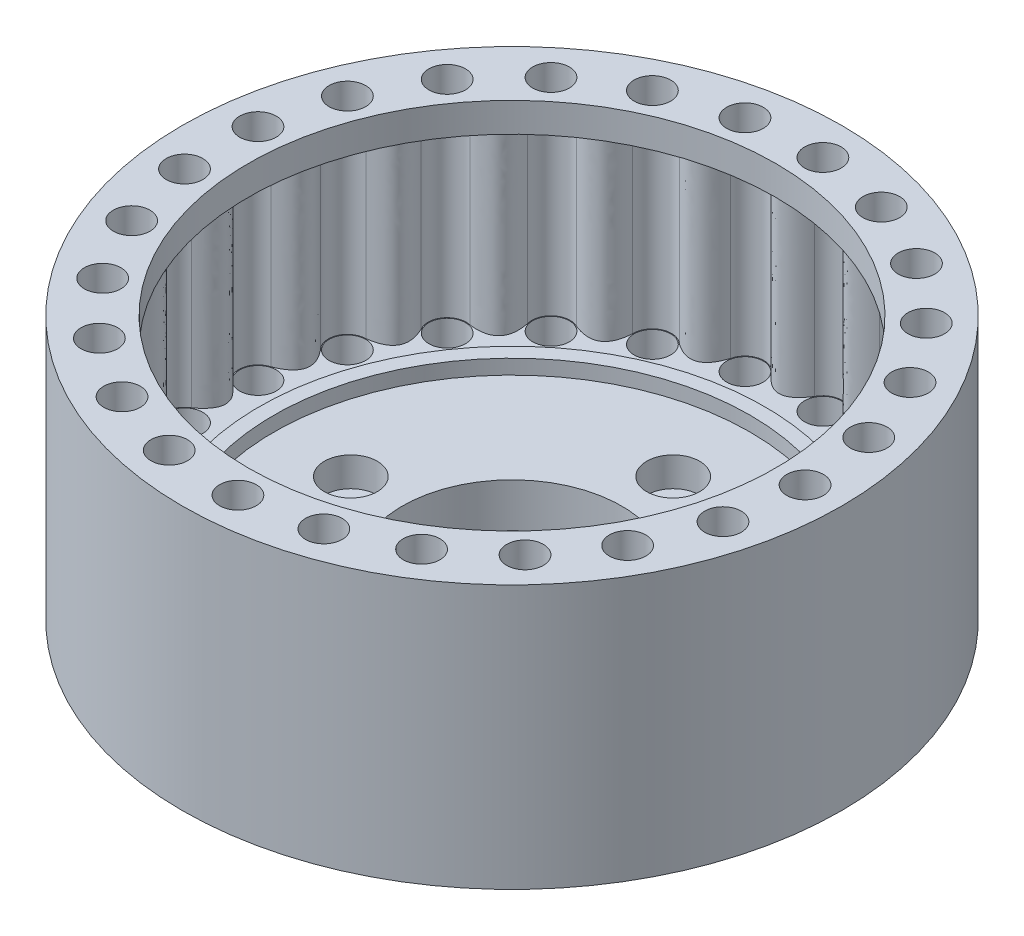
SolidWorks part; units mm, degrees
ref_plane "Front Plane" through (0, 0, 0) normal (0, 0, 1) x (1, 0, 0)
ref_plane "Top Plane" through (0, 0, 0) normal (0, 1, 0) x (1, 0, 0)
ref_plane "Right Plane" through (0, 0, 0) normal (1, 0, 0) x (0, 0, -1)
sketch "Sketch1" plane through (0, 0, 0) normal (0, 1, 0) x (1, 0, 0)
  circle A1 centre (0, 0) radius 45
  circle A2 centre (0, 0) radius 22 construction
  circle A3 centre (0, -22) radius 2
  circle A5 centre (-22, 0) radius 2
  circle A6 centre (0, 22) radius 2
  circle A7 centre (22, 0) radius 2
  point P15 (0, 0)
  dimension "D1" = 90
  dimension "D2" = 44
  dimension "D3" = 4
  dimension "D4" = 4
  dimension "D5" = 90
  dimension "D6" = 22
extrude "Boss-Extrude1" add sketch "Sketch1" along normal blind 6
sketch "Sketch2" plane through (0, 6, 0) normal (0, 1, 0) x (1, 0, 0)
  circle A0 centre (0, 0) radius 22 construction
  circle A1 centre (0, 22) radius 3.61
  circle A2 centre (22, 0) radius 3.61
  circle A3 centre (0, -22) radius 3.61
  circle A4 centre (-22, 0) radius 3.61
  point P14 (0, 0)
  dimension "D1" = 44
  dimension "D2" = 7.22
  dimension "D4" = 22
  dimension "D5" = 90
  dimension "D3" = 4
extrude "Cut-Extrude1" cut sketch "Sketch2" against normal blind 4
sketch "Sketch4" plane through (0, 6, 0) normal (0, 1, 0) x (1, 0, 0)
  circle A0 centre (0, 0) radius 15
  dimension "D1" = 30
extrude "Cut-Extrude2" cut sketch "Sketch4" against normal through all
sketch "Sketch5" plane through (0, 6, 0) normal (0, 1, 0) x (1, 0, 0)
  circle A0 centre (40, 0) radius 2.5
  circle A1 centre (38.7433, -9.9476) radius 2.5
  circle A2 centre (35.0523, -19.2701) radius 2.5
  circle A3 centre (29.1587, -27.3819) radius 2.5
  circle A4 centre (21.4331, -33.7731) radius 2.5
  circle A5 centre (12.3607, -38.0423) radius 2.5
  circle A6 centre (2.5116, -39.9211) radius 2.5
  circle A7 centre (-7.4953, -39.2915) radius 2.5
  circle A8 centre (-17.0312, -36.1931) radius 2.5
  circle A9 centre (-25.497, -30.8205) radius 2.5
  circle A10 centre (-32.3607, -23.5114) radius 2.5
  circle A11 centre (-37.1911, -14.725) radius 2.5
  circle A12 centre (-39.6846, -5.0133) radius 2.5
  circle A13 centre (-39.6846, 5.0133) radius 2.5
  circle A14 centre (-37.1911, 14.725) radius 2.5
  circle A15 centre (-32.3607, 23.5114) radius 2.5
  circle A16 centre (-25.497, 30.8205) radius 2.5
  circle A17 centre (-17.0312, 36.1931) radius 2.5
  circle A18 centre (-7.4953, 39.2915) radius 2.5
  circle A19 centre (2.5116, 39.9211) radius 2.5
  circle A20 centre (12.3607, 38.0423) radius 2.5
  circle A21 centre (21.4331, 33.7731) radius 2.5
  circle A22 centre (29.1587, 27.3819) radius 2.5
  circle A23 centre (35.0523, 19.2701) radius 2.5
  circle A24 centre (38.7433, 9.9476) radius 2.5
  point P53 (0, 0)
  dimension "D2" = 5
  dimension "D1" = 40
  dimension "D3" = 25
extrude "Cut-Extrude3" cut sketch "Sketch5" against normal blind 4
sketch "Sketch6" plane through (0, 6, 0) normal (0, 1, 0) x (1, 0, 0)
  circle A0 centre (0, 0) radius 32.5
  circle A1 centre (0, 0) radius 34.5
  dimension "D1" = 65
  dimension "D2" = 69
extrude "Boss-Extrude2" add sketch "Sketch6" along normal blind 2
sketch "Sketch7" plane through (0, 6, 0) normal (0, 1, 0) x (1, 0, 0)
  line L0 (0, 0) -> (35.0523, -19.2701) construction
  line L1 (0, 0) -> (27.3363, -25.6705) construction
  line L2 (35.0523, -19.2701) -> (34.7909, -21.7565) construction
  line L3 (29.1587, -27.3819) -> (31.4426, -26.365) construction
  line L4 (0, 0) -> (31.5517, -22.9236) construction
  circle A0 centre (35.0523, -19.2701) radius 2.5 construction
  circle A1 centre (38.7433, -9.9476) radius 2.5 construction
  circle A2 centre (40, 0) radius 2.5 construction
  circle A3 centre (38.7433, 9.9476) radius 2.5 construction
  circle A4 centre (35.0523, 19.2701) radius 2.5 construction
  circle A5 centre (29.1587, 27.3819) radius 2.5 construction
  circle A6 centre (21.4331, 33.7731) radius 2.5 construction
  circle A7 centre (12.3607, 38.0423) radius 2.5 construction
  circle A8 centre (2.5116, 39.9211) radius 2.5 construction
  circle A9 centre (-7.4953, 39.2915) radius 2.5 construction
  circle A10 centre (-17.0312, 36.1931) radius 2.5 construction
  circle A11 centre (-25.497, 30.8205) radius 2.5 construction
  circle A12 centre (-32.3607, 23.5114) radius 2.5 construction
  circle A13 centre (-37.1911, 14.725) radius 2.5 construction
  circle A14 centre (-39.6846, 5.0133) radius 2.5 construction
  circle A15 centre (-39.6846, -5.0133) radius 2.5 construction
  circle A16 centre (-37.1911, -14.725) radius 2.5 construction
  circle A17 centre (-32.3607, -23.5114) radius 2.5 construction
  circle A18 centre (-25.497, -30.8205) radius 2.5 construction
  circle A19 centre (-17.0312, -36.1931) radius 2.5 construction
  circle A20 centre (-7.4953, -39.2915) radius 2.5 construction
  circle A21 centre (2.5116, -39.9211) radius 2.5 construction
  circle A22 centre (12.3607, -38.0423) radius 2.5 construction
  circle A23 centre (21.4331, -33.7731) radius 2.5 construction
  circle A24 centre (29.1587, -27.3819) radius 2.5 construction
  arc A25 (34.7909, -21.7565) -> (37.0115, -17.7173) centre (35.0523, -19.2701) ccw construction
  arc A26 (39.1085, -12.4208) -> (40.2548, -7.9563) centre (38.7433, -9.9476) ccw construction
  arc A27 (40.9688, -2.3047) -> (40.9688, 2.3047) centre (40, 0) ccw construction
  arc A28 (40.2548, 7.9563) -> (39.1085, 12.4208) centre (38.7433, 9.9476) ccw construction
  arc A29 (37.0115, 17.7173) -> (34.7909, 21.7565) centre (35.0523, 19.2701) ccw construction
  arc A30 (31.4426, 26.365) -> (28.2873, 29.7251) centre (29.1587, 27.3819) ccw construction
  arc A31 (23.8981, 33.3562) -> (20.0063, 35.826) centre (21.4331, 33.7731) ccw construction
  arc A32 (14.8519, 38.2515) -> (10.4682, 39.6758) centre (12.3607, 38.0423) ccw construction
  arc A33 (4.8726, 40.7432) -> (0.2723, 41.0327) centre (2.5116, 39.9211) ccw construction
  arc A34 (-5.4129, 40.675) -> (-9.9406, 39.8113) centre (-7.4953, 39.2915) ccw construction
  arc A35 (-15.3583, 38.0509) -> (-19.529, 36.0884) centre (-17.0312, 36.1931) ccw construction
  arc A36 (-24.3387, 33.036) -> (-27.8903, 30.098) centre (-25.497, 30.8205) ccw construction
  arc A37 (-31.7898, 25.9454) -> (-34.4991, 22.2163) centre (-32.3607, 23.5114) ccw construction
  arc A38 (-37.2434, 17.2244) -> (-38.9402, 12.9388) centre (-37.1911, 14.725) ccw construction
  arc A39 (-40.3569, 7.4212) -> (-40.9346, 2.8483) centre (-39.6846, 5.0133) ccw construction
  arc A40 (-40.9346, -2.8483) -> (-40.3569, -7.4212) centre (-39.6846, -5.0133) ccw construction
  arc A41 (-38.9402, -12.9388) -> (-37.2434, -17.2244) centre (-37.1911, -14.725) ccw construction
  arc A42 (-34.4991, -22.2163) -> (-31.7898, -25.9454) centre (-32.3607, -23.5114) ccw construction
  arc A43 (-27.8903, -30.098) -> (-24.3387, -33.036) centre (-25.497, -30.8205) ccw construction
  arc A44 (-19.529, -36.0884) -> (-15.3583, -38.0509) centre (-17.0312, -36.1931) ccw construction
  arc A45 (-9.9406, -39.8113) -> (-5.4129, -40.675) centre (-7.4953, -39.2915) ccw construction
  arc A46 (0.2723, -41.0327) -> (4.8726, -40.7432) centre (2.5116, -39.9211) ccw construction
  arc A47 (10.4682, -39.6758) -> (14.8519, -38.2515) centre (12.3607, -38.0423) ccw construction
  arc A48 (20.0063, -35.826) -> (23.8981, -33.3562) centre (21.4331, -33.7731) ccw construction
  arc A49 (28.2873, -29.7251) -> (31.4426, -26.365) centre (29.1587, -27.3819) ccw construction
  arc A51 (33.4936, -21.8672) -> (35.0523, -19.2701) centre (0, 0) ccw construction
  arc A53 (23.9272, -32.0545) -> (27.0032, -29.5098) centre (0, 0) ccw construction
  arc A54 (15.2038, -36.9979) -> (18.8161, -35.2981) centre (0, 0) ccw construction
  arc A55 (9.9601, -38.7401) -> (14.713, -37.1958) centre (0, 0) ccw construction
  arc A56 (5.5252, -39.6166) -> (9.4467, -38.8685) centre (0, 0) ccw construction
  arc A57 (-5.0261, -39.683) -> (5.0006, -39.6862) centre (0, 0) ccw construction
  arc A58 (-14.7369, -37.1863) -> (-10.4469, -38.6117) centre (0, 0) ccw construction
  arc A59 (-23.0917, -32.6615) -> (-22.9047, -32.7929) centre (0, 0) ccw construction
  arc A60 (-30.4888, -25.8927) -> (-27.756, -28.8029) centre (0, 0) ccw construction
  arc A61 (-35.9702, -17.4969) -> (-34.047, -20.9953) centre (0, 0) ccw construction
  arc A62 (-39.1915, -8.0018) -> (-38.1986, -11.8686) centre (0, 0) ccw construction
  arc A63 (-39.9502, 1.9961) -> (-39.9502, -1.9961) centre (0, 0) ccw construction
  arc A64 (-38.1986, 11.8686) -> (-39.1915, 8.0018) centre (0, 0) ccw construction
  arc A65 (-36.1986, 17.0195) -> (-38.0383, 12.3729) centre (0, 0) ccw construction
  arc A66 (-34.047, 20.9953) -> (-35.9702, 17.4969) centre (0, 0) ccw construction
  arc A67 (-27.756, 28.8029) -> (-30.4888, 25.8927) centre (0, 0) ccw construction
  arc A68 (-19.2589, 35.0585) -> (-23.0917, 32.6615) centre (0, 0) ccw construction
  arc A69 (-9.9351, 38.7465) -> (-14.7369, 37.1863) centre (0, 0) ccw construction
  arc A70 (-0.5163, 39.9967) -> (-5.0261, 39.683) centre (0, 0) ccw construction
  arc A71 (9.4467, 38.8685) -> (0.0129, 40) centre (0, 0) ccw construction
  arc A72 (18.8161, 35.2981) -> (15.2038, 36.9979) centre (0, 0) ccw construction
  arc A73 (27.0032, 29.5098) -> (23.9272, 32.0545) centre (0, 0) ccw construction
  arc A74 (33.4936, 21.8672) -> (30.8123, 25.5069) centre (0, 0) ccw construction
  arc A75 (37.8795, 12.8507) -> (36.4099, 16.5626) centre (0, 0) ccw construction
  arc A76 (39.8853, 3.0267) -> (39.2891, 7.5079) centre (0, 0) ccw construction
  arc A77 (39.385, -6.9875) -> (39.9219, -2.4988) centre (0, 0) ccw construction
  arc A78 (36.1876, -17.0428) -> (37.8795, -12.8507) centre (0, 0) ccw construction
  circle A79 centre (0, 0) radius 45
  arc A80 (34.7861, -21.8565) -> (37.0934, -17.6596) centre (35.0523, -19.2701) ccw
  arc A81 (39.1287, -12.5189) -> (40.3198, -7.88) centre (38.7433, -9.9476) ccw
  arc A82 (41.0127, -2.3947) -> (41.0127, 2.3947) centre (40, 0) ccw
  arc A83 (40.3198, 7.88) -> (39.1287, 12.5189) centre (38.7433, 9.9476) ccw
  arc A84 (37.0934, 17.6596) -> (34.7861, 21.8565) centre (35.0523, 19.2701) ccw
  arc A85 (31.5362, 26.3295) -> (28.2577, 29.8208) centre (29.1587, 27.3819) ccw
  arc A86 (23.9976, 33.3451) -> (19.9538, 35.9113) centre (21.4331, 33.7731) ccw
  arc A87 (14.9511, 38.2654) -> (10.3962, 39.7454) centre (12.3607, 38.0423) ccw
  arc A88 (4.9651, 40.7814) -> (0.1853, 41.0822) centre (2.5116, 39.9211) ccw
  arc A89 (-5.3328, 40.735) -> (-10.0373, 39.8376) centre (-7.4953, 39.2915) ccw
  arc A90 (-15.2956, 38.129) -> (-19.6291, 36.0898) centre (-17.0312, 36.1931) ccw
  arc A91 (-24.2974, 33.1273) -> (-27.9876, 30.0744) centre (-25.497, 30.8205) ccw
  arc A92 (-31.7724, 26.044) -> (-34.5875, 22.1694) centre (-32.3607, 23.5114) ccw
  arc A93 (-37.2511, 17.3243) -> (-39.0142, 12.8713) centre (-37.1911, 14.725) ccw
  arc A94 (-40.3892, 7.516) -> (-40.9895, 2.7645) centre (-39.6846, 5.0133) ccw
  arc A95 (-40.9895, -2.7645) -> (-40.3892, -7.516) centre (-39.6846, -5.0133) ccw
  arc A96 (-39.0142, -12.8713) -> (-37.2511, -17.3243) centre (-37.1911, -14.725) ccw
  arc A97 (-34.5875, -22.1694) -> (-31.7724, -26.044) centre (-32.3607, -23.5114) ccw
  arc A98 (-27.9876, -30.0744) -> (-24.2974, -33.1273) centre (-25.497, -30.8205) ccw
  arc A99 (-19.6291, -36.0898) -> (-15.2956, -38.129) centre (-17.0312, -36.1931) ccw
  arc A100 (-10.0373, -39.8376) -> (-5.3328, -40.735) centre (-7.4953, -39.2915) ccw
  arc A101 (0.1853, -41.0822) -> (4.9651, -40.7814) centre (2.5116, -39.9211) ccw
  arc A102 (10.3962, -39.7454) -> (14.9511, -38.2654) centre (12.3607, -38.0423) ccw
  arc A103 (19.9538, -35.9113) -> (23.9976, -33.3451) centre (21.4331, -33.7731) ccw
  arc A104 (28.2577, -29.8208) -> (31.5362, -26.3295) centre (29.1587, -27.3819) ccw
  spline S0 degree 2 poles (34.7909, -21.7565) (29.9865, -21.7865) (31.4426, -26.365) knots 0 0 0 1 1 1 construction
  spline S1 degree 2 poles (28.2873, -29.7251) (23.6264, -28.5594) (23.8981, -33.3562) knots 0 0 0 1 1 1 construction
  spline S2 degree 2 poles (20.0063, -35.826) (15.7817, -33.5378) (14.8519, -38.2515) knots 0 0 0 1 1 1 construction
  spline S3 degree 2 poles (10.4682, -39.6758) (6.9454, -36.4089) (4.8726, -40.7432) knots 0 0 0 1 1 1 construction
  spline S4 degree 2 poles (0.2723, -41.0327) (-2.3274, -36.9923) (-5.4129, -40.675) knots 0 0 0 1 1 1 construction
  spline S5 degree 2 poles (-9.9406, -39.8113) (-11.4538, -35.2513) (-15.3583, -38.0509) knots 0 0 0 1 1 1 construction
  spline S6 degree 2 poles (-19.529, -36.0884) (-19.8606, -31.2954) (-24.3387, -33.036) knots 0 0 0 1 1 1 construction
  spline S7 degree 2 poles (-27.8903, -30.098) (-27.0195, -25.373) (-31.7898, -25.9454) knots 0 0 0 1 1 1 construction
  spline S8 degree 2 poles (-34.4991, -22.2163) (-32.4807, -17.8564) (-37.2434, -17.2244) knots 0 0 0 1 1 1 construction
  spline S9 degree 2 poles (-38.9402, -12.9388) (-35.9009, -9.2178) (-40.3569, -7.4212) knots 0 0 0 1 1 1 construction
  spline S10 degree 2 poles (-40.9346, -2.8483) (-37.0654, 0) (-40.9346, 2.8483) knots 0 0 0 1 1 1 construction
  spline S11 degree 2 poles (-40.3569, 7.4212) (-35.9009, 9.2178) (-38.9402, 12.9388) knots 0 0 0 1 1 1 construction
  spline S12 degree 2 poles (-37.2434, 17.2244) (-32.4807, 17.8564) (-34.4991, 22.2163) knots 0 0 0 1 1 1 construction
  spline S13 degree 2 poles (-31.7898, 25.9454) (-27.0195, 25.373) (-27.8903, 30.098) knots 0 0 0 1 1 1 construction
  spline S14 degree 2 poles (-24.3387, 33.036) (-19.8606, 31.2954) (-19.529, 36.0884) knots 0 0 0 1 1 1 construction
  spline S15 degree 2 poles (-15.3583, 38.0509) (-11.4538, 35.2513) (-9.9406, 39.8113) knots 0 0 0 1 1 1 construction
  spline S16 degree 2 poles (-5.4129, 40.675) (-2.3274, 36.9923) (0.2723, 41.0327) knots 0 0 0 1 1 1 construction
  spline S17 degree 2 poles (4.8726, 40.7432) (6.9454, 36.4089) (10.4682, 39.6758) knots 0 0 0 1 1 1 construction
  spline S18 degree 2 poles (14.8519, 38.2515) (15.7817, 33.5378) (20.0063, 35.826) knots 0 0 0 1 1 1 construction
  spline S19 degree 2 poles (23.8981, 33.3562) (23.6264, 28.5594) (28.2873, 29.7251) knots 0 0 0 1 1 1 construction
  spline S20 degree 2 poles (31.4426, 26.365) (29.9865, 21.7865) (34.7909, 21.7565) knots 0 0 0 1 1 1 construction
  spline S21 degree 2 poles (37.0115, 17.7173) (34.4625, 13.6447) (39.1085, 12.4208) knots 0 0 0 1 1 1 construction
  spline S22 degree 2 poles (40.2548, 7.9563) (36.7731, 4.6455) (40.9688, 2.3047) knots 0 0 0 1 1 1 construction
  spline S23 degree 2 poles (40.9688, -2.3047) (36.7731, -4.6455) (40.2548, -7.9563) knots 0 0 0 1 1 1 construction
  spline S24 degree 2 poles (39.1085, -12.4208) (34.4625, -13.6447) (37.0115, -17.7173) knots 0 0 0 1 1 1 construction
  spline S25 degree 1 poles (39.1287, -12.5189) (37.0934, -17.6596) knots 0 0 1 1 construction
  spline S26 degree 1 poles (41.0127, -2.3947) (40.3198, -7.88) knots 0 0 1 1 construction
  spline S27 degree 1 poles (40.3198, 7.88) (41.0127, 2.3947) knots 0 0 1 1 construction
  spline S28 degree 1 poles (37.0934, 17.6596) (39.1287, 12.5189) knots 0 0 1 1 construction
  spline S29 degree 1 poles (31.5362, 26.3295) (34.7861, 21.8565) knots 0 0 1 1 construction
  spline S30 degree 1 poles (23.9976, 33.3451) (28.2577, 29.8208) knots 0 0 1 1 construction
  spline S31 degree 1 poles (14.9511, 38.2654) (19.9538, 35.9113) knots 0 0 1 1 construction
  spline S32 degree 1 poles (4.9651, 40.7814) (10.3962, 39.7454) knots 0 0 1 1 construction
  spline S33 degree 1 poles (-5.3328, 40.735) (0.1853, 41.0822) knots 0 0 1 1 construction
  spline S34 degree 1 poles (-15.2956, 38.129) (-10.0373, 39.8376) knots 0 0 1 1 construction
  spline S35 degree 1 poles (-24.2974, 33.1273) (-19.6291, 36.0898) knots 0 0 1 1 construction
  spline S36 degree 1 poles (-31.7724, 26.044) (-27.9876, 30.0744) knots 0 0 1 1 construction
  spline S37 degree 1 poles (-37.2511, 17.3243) (-34.5875, 22.1694) knots 0 0 1 1 construction
  spline S38 degree 1 poles (-40.3892, 7.516) (-39.0142, 12.8713) knots 0 0 1 1 construction
  spline S39 degree 1 poles (-40.9895, -2.7645) (-40.9895, 2.7645) knots 0 0 1 1 construction
  spline S40 degree 1 poles (-39.0142, -12.8713) (-40.3892, -7.516) knots 0 0 1 1 construction
  spline S41 degree 1 poles (-34.5875, -22.1694) (-37.2511, -17.3243) knots 0 0 1 1 construction
  spline S42 degree 1 poles (-27.9876, -30.0744) (-31.7724, -26.044) knots 0 0 1 1 construction
  spline S43 degree 1 poles (-19.6291, -36.0898) (-24.2974, -33.1273) knots 0 0 1 1 construction
  spline S44 degree 1 poles (-10.0373, -39.8376) (-15.2956, -38.129) knots 0 0 1 1 construction
  spline S45 degree 1 poles (0.1853, -41.0822) (-5.3328, -40.735) knots 0 0 1 1 construction
  spline S46 degree 1 poles (10.3962, -39.7454) (4.9651, -40.7814) knots 0 0 1 1 construction
  spline S47 degree 1 poles (19.9538, -35.9113) (14.9511, -38.2654) knots 0 0 1 1 construction
  spline S48 degree 1 poles (28.2577, -29.8208) (23.9976, -33.3451) knots 0 0 1 1 construction
  spline S49 degree 1 poles (34.7861, -21.8565) (31.5362, -26.3295) knots 0 0 1 1 construction
  spline S50 degree 3 poles (37.0934, -17.6596) (36.9928, -17.4988) (36.7956, -17.161) (36.4917, -16.5417) (36.2467, -15.8185) (36.1759, -15.0518) (36.3187, -14.3796) (36.6748, -13.7918) (37.2512, -13.2814) (37.9249, -12.9219) (38.5703, -12.6785) (38.9453, -12.5673) (39.1287, -12.5189) knots 0.000577 0.000577 0.000577 0.000577 0.063005 0.125433 0.250288 0.375144 0.5 0.624856 0.749712 0.874567 0.936995 0.999423 0.999423 0.999423 0.999423
  spline S51 degree 3 poles (40.3198, -7.88) (40.1824, -7.7493) (39.9074, -7.4711) (39.459, -6.9469) (39.0418, -6.3073) (38.7826, -5.5824) (38.7538, -4.8957) (38.9524, -4.2379) (39.3838, -3.6001) (39.947, -3.0844) (40.5116, -2.6882) (40.8472, -2.4872) (41.0127, -2.3947) knots 0.000577 0.000577 0.000577 0.000577 0.063005 0.125433 0.250288 0.375144 0.5 0.624856 0.749712 0.874567 0.936995 0.999423 0.999423 0.999423 0.999423
  spline S52 degree 3 poles (41.0127, 2.3947) (40.8472, 2.4872) (40.5116, 2.6882) (39.947, 3.0844) (39.3838, 3.6001) (38.9524, 4.2379) (38.7538, 4.8957) (38.7826, 5.5824) (39.0418, 6.3073) (39.459, 6.9469) (39.9074, 7.4711) (40.1824, 7.7493) (40.3198, 7.88) knots 0.000577 0.000577 0.000577 0.000577 0.063005 0.125433 0.250288 0.375144 0.5 0.624856 0.749712 0.874567 0.936995 0.999423 0.999423 0.999423 0.999423
  spline S53 degree 3 poles (39.1287, 12.5189) (38.9453, 12.5673) (38.5703, 12.6785) (37.9249, 12.9219) (37.2512, 13.2814) (36.6748, 13.7918) (36.3187, 14.3796) (36.1759, 15.0518) (36.2467, 15.8185) (36.4917, 16.5417) (36.7956, 17.161) (36.9928, 17.4988) (37.0934, 17.6596) knots 0.000577 0.000577 0.000577 0.000577 0.063005 0.125433 0.250288 0.375144 0.5 0.624856 0.749712 0.874567 0.936995 0.999423 0.999423 0.999423 0.999423
  spline S54 degree 3 poles (34.7861, 21.8565) (34.5964, 21.8578) (34.2055, 21.8722) (33.5199, 21.9475) (32.7779, 22.1281) (32.0927, 22.4791) (31.6016, 22.9599) (31.2961, 23.5755) (31.174, 24.3357) (31.2315, 25.0971) (31.3718, 25.7725) (31.4789, 26.1488) (31.5362, 26.3295) knots 0.000577 0.000577 0.000577 0.000577 0.063005 0.125433 0.250288 0.375144 0.5 0.624856 0.749712 0.874567 0.936995 0.999423 0.999423 0.999423 0.999423
  spline S55 degree 3 poles (28.2577, 29.8208) (28.0737, 29.7749) (27.6915, 29.6917) (27.0087, 29.594) (26.2451, 29.5845) (25.4941, 29.754) (24.8989, 30.0976) (24.4499, 30.6179) (24.1426, 31.3238) (24.0089, 32.0756) (23.9769, 32.7647) (23.987, 33.1557) (23.9976, 33.3451) knots 0.000577 0.000577 0.000577 0.000577 0.063005 0.125433 0.250288 0.375144 0.5 0.624856 0.749712 0.874567 0.936995 0.999423 0.999423 0.999423 0.999423
  spline S56 degree 3 poles (19.9538, 35.9113) (19.787, 35.8211) (19.4375, 35.6454) (18.8004, 35.3811) (18.0632, 35.1819) (17.2936, 35.1594) (16.6317, 35.3442) (16.0674, 35.7364) (15.5942, 36.3437) (15.2777, 37.0387) (15.0754, 37.6981) (14.9879, 38.0794) (14.9511, 38.2654) knots 0.000577 0.000577 0.000577 0.000577 0.063005 0.125433 0.250288 0.375144 0.5 0.624856 0.749712 0.874567 0.936995 0.999423 0.999423 0.999423 0.999423
  spline S57 degree 3 poles (10.3962, 39.7454) (10.257, 39.6165) (9.9622, 39.3595) (9.4108, 38.945) (8.7463, 38.5687) (8.0065, 38.3555) (7.3194, 38.3699) (6.6753, 38.6095) (6.0659, 39.08) (5.5866, 39.6745) (5.2266, 40.2629) (5.0471, 40.6104) (4.9651, 40.7814) knots 0.000577 0.000577 0.000577 0.000577 0.063005 0.125433 0.250288 0.375144 0.5 0.624856 0.749712 0.874567 0.936995 0.999423 0.999423 0.999423 0.999423
  spline S58 degree 3 poles (0.1853, 41.0822) (0.0826, 40.9227) (-0.1391, 40.6004) (-0.57, 40.0618) (-1.1201, 39.5321) (-1.7837, 39.1417) (-2.4527, 38.9847) (-3.1362, 39.0566) (-3.8434, 39.3608) (-4.4555, 39.8174) (-4.9506, 40.2977) (-5.2109, 40.5897) (-5.3328, 40.735) knots 0.000577 0.000577 0.000577 0.000577 0.063005 0.125433 0.250288 0.375144 0.5 0.624856 0.749712 0.874567 0.936995 0.999423 0.999423 0.999423 0.999423
  spline S59 degree 3 poles (-10.0373, 39.8376) (-10.0971, 39.6576) (-10.2317, 39.2903) (-10.5151, 38.6614) (-10.9161, 38.0116) (-11.4618, 37.4684) (-12.0708, 37.15) (-12.7506, 37.0496) (-13.5113, 37.1684) (-14.2177, 37.4584) (-14.8167, 37.8005) (-15.1414, 38.0186) (-15.2956, 38.129) knots 0.000577 0.000577 0.000577 0.000577 0.063005 0.125433 0.250288 0.375144 0.5 0.624856 0.749712 0.874567 0.936995 0.999423 0.999423 0.999423 0.999423
  spline S60 degree 3 poles (-19.6291, 36.0898) (-19.6423, 35.9006) (-19.6813, 35.5114) (-19.7995, 34.8318) (-20.0263, 34.1027) (-20.4197, 33.4408) (-20.9303, 32.981) (-21.5639, 32.7147) (-22.3302, 32.6406) (-23.0866, 32.7458) (-23.7518, 32.9282) (-24.1206, 33.0586) (-24.2974, 33.1273) knots 0.000577 0.000577 0.000577 0.000577 0.063005 0.125433 0.250288 0.375144 0.5 0.624856 0.749712 0.874567 0.936995 0.999423 0.999423 0.999423 0.999423
  spline S61 degree 3 poles (-27.9876, 30.0744) (-27.9533, 29.8879) (-27.8943, 29.5012) (-27.8397, 28.8136) (-27.8781, 28.0509) (-28.0945, 27.3121) (-28.4748, 26.7396) (-29.0222, 26.3242) (-29.7461, 26.0618) (-30.5048, 25.9756) (-31.1945, 25.9869) (-31.5841, 26.0215) (-31.7724, 26.044) knots 0.000577 0.000577 0.000577 0.000577 0.063005 0.125433 0.250288 0.375144 0.5 0.624856 0.749712 0.874567 0.936995 0.999423 0.999423 0.999423 0.999423
  spline S62 degree 3 poles (-34.5875, 22.1694) (-34.508, 21.9972) (-34.3546, 21.6373) (-34.1308, 20.9849) (-33.9783, 20.2367) (-34.0041, 19.4672) (-34.2301, 18.8182) (-34.657, 18.2796) (-35.2928, 17.8455) (-36.0063, 17.5733) (-36.6771, 17.4127) (-37.0631, 17.3493) (-37.2511, 17.3243) knots 0.000577 0.000577 0.000577 0.000577 0.063005 0.125433 0.250288 0.375144 0.5 0.624856 0.749712 0.874567 0.936995 0.999423 0.999423 0.999423 0.999423
  spline S63 degree 3 poles (-39.0142, 12.8713) (-38.8943, 12.7243) (-38.6563, 12.4139) (-38.2772, 11.8376) (-37.9434, 11.1508) (-37.7771, 10.3991) (-37.8346, 9.7143) (-38.1141, 9.0865) (-38.622, 8.5078) (-39.2454, 8.0668) (-39.8552, 7.7444) (-40.2133, 7.587) (-40.3892, 7.516) knots 0.000577 0.000577 0.000577 0.000577 0.063005 0.125433 0.250288 0.375144 0.5 0.624856 0.749712 0.874567 0.936995 0.999423 0.999423 0.999423 0.999423
  spline S64 degree 3 poles (-40.9895, 2.7645) (-40.8368, 2.652) (-40.5291, 2.4105) (-40.0186, 1.9466) (-39.5245, 1.3644) (-39.1764, 0.6776) (-39.0618, 0) (-39.1764, -0.6776) (-39.5245, -1.3644) (-40.0186, -1.9466) (-40.5291, -2.4105) (-40.8368, -2.652) (-40.9895, -2.7645) knots 0.000577 0.000577 0.000577 0.000577 0.063005 0.125433 0.250288 0.375144 0.5 0.624856 0.749712 0.874567 0.936995 0.999423 0.999423 0.999423 0.999423
  spline S65 degree 3 poles (-40.3892, -7.516) (-40.2133, -7.587) (-39.8552, -7.7444) (-39.2454, -8.0668) (-38.622, -8.5078) (-38.1141, -9.0865) (-37.8346, -9.7143) (-37.7771, -10.3991) (-37.9434, -11.1508) (-38.2772, -11.8376) (-38.6563, -12.4139) (-38.8943, -12.7243) (-39.0142, -12.8713) knots 0.000577 0.000577 0.000577 0.000577 0.063005 0.125433 0.250288 0.375144 0.5 0.624856 0.749712 0.874567 0.936995 0.999423 0.999423 0.999423 0.999423
  spline S66 degree 3 poles (-37.2511, -17.3243) (-37.0631, -17.3493) (-36.6771, -17.4127) (-36.0063, -17.5733) (-35.2928, -17.8455) (-34.657, -18.2796) (-34.2301, -18.8182) (-34.0041, -19.4672) (-33.9783, -20.2367) (-34.1308, -20.9849) (-34.3546, -21.6373) (-34.508, -21.9972) (-34.5875, -22.1694) knots 0.000577 0.000577 0.000577 0.000577 0.063005 0.125433 0.250288 0.375144 0.5 0.624856 0.749712 0.874567 0.936995 0.999423 0.999423 0.999423 0.999423
  spline S67 degree 3 poles (-31.7724, -26.044) (-31.5841, -26.0215) (-31.1945, -25.9869) (-30.5048, -25.9756) (-29.7461, -26.0618) (-29.0222, -26.3242) (-28.4748, -26.7396) (-28.0945, -27.3121) (-27.8781, -28.0509) (-27.8397, -28.8136) (-27.8943, -29.5012) (-27.9533, -29.8879) (-27.9876, -30.0744) knots 0.000577 0.000577 0.000577 0.000577 0.063005 0.125433 0.250288 0.375144 0.5 0.624856 0.749712 0.874567 0.936995 0.999423 0.999423 0.999423 0.999423
  spline S68 degree 3 poles (-24.2974, -33.1273) (-24.1206, -33.0586) (-23.7518, -32.9282) (-23.0866, -32.7458) (-22.3302, -32.6406) (-21.5639, -32.7147) (-20.9303, -32.981) (-20.4197, -33.4408) (-20.0263, -34.1027) (-19.7995, -34.8318) (-19.6813, -35.5114) (-19.6423, -35.9006) (-19.6291, -36.0898) knots 0.000577 0.000577 0.000577 0.000577 0.063005 0.125433 0.250288 0.375144 0.5 0.624856 0.749712 0.874567 0.936995 0.999423 0.999423 0.999423 0.999423
  spline S69 degree 3 poles (-15.2956, -38.129) (-15.1414, -38.0186) (-14.8167, -37.8005) (-14.2177, -37.4584) (-13.5113, -37.1684) (-12.7506, -37.0496) (-12.0708, -37.15) (-11.4618, -37.4684) (-10.9161, -38.0116) (-10.5151, -38.6614) (-10.2317, -39.2903) (-10.0971, -39.6576) (-10.0373, -39.8376) knots 0.000577 0.000577 0.000577 0.000577 0.063005 0.125433 0.250288 0.375144 0.5 0.624856 0.749712 0.874567 0.936995 0.999423 0.999423 0.999423 0.999423
  spline S70 degree 3 poles (-5.3328, -40.735) (-5.2109, -40.5897) (-4.9506, -40.2977) (-4.4555, -39.8174) (-3.8434, -39.3608) (-3.1362, -39.0566) (-2.4527, -38.9847) (-1.7837, -39.1417) (-1.1201, -39.5321) (-0.57, -40.0618) (-0.1391, -40.6004) (0.0826, -40.9227) (0.1853, -41.0822) knots 0.000577 0.000577 0.000577 0.000577 0.063005 0.125433 0.250288 0.375144 0.5 0.624856 0.749712 0.874567 0.936995 0.999423 0.999423 0.999423 0.999423
  spline S71 degree 3 poles (4.9651, -40.7814) (5.0471, -40.6104) (5.2266, -40.2629) (5.5866, -39.6745) (6.0659, -39.08) (6.6753, -38.6095) (7.3194, -38.3699) (8.0065, -38.3555) (8.7463, -38.5687) (9.4108, -38.945) (9.9622, -39.3595) (10.257, -39.6165) (10.3962, -39.7454) knots 0.000577 0.000577 0.000577 0.000577 0.063005 0.125433 0.250288 0.375144 0.5 0.624856 0.749712 0.874567 0.936995 0.999423 0.999423 0.999423 0.999423
  spline S72 degree 3 poles (14.9511, -38.2654) (14.9879, -38.0794) (15.0754, -37.6981) (15.2777, -37.0387) (15.5942, -36.3437) (16.0674, -35.7364) (16.6317, -35.3442) (17.2936, -35.1594) (18.0632, -35.1819) (18.8004, -35.3811) (19.4375, -35.6454) (19.787, -35.8211) (19.9538, -35.9113) knots 0.000577 0.000577 0.000577 0.000577 0.063005 0.125433 0.250288 0.375144 0.5 0.624856 0.749712 0.874567 0.936995 0.999423 0.999423 0.999423 0.999423
  spline S73 degree 3 poles (23.9976, -33.3451) (23.987, -33.1557) (23.9769, -32.7647) (24.0089, -32.0756) (24.1426, -31.3238) (24.4499, -30.6179) (24.8989, -30.0976) (25.4941, -29.754) (26.2451, -29.5845) (27.0087, -29.594) (27.6915, -29.6917) (28.0737, -29.7749) (28.2577, -29.8208) knots 0.000577 0.000577 0.000577 0.000577 0.063005 0.125433 0.250288 0.375144 0.5 0.624856 0.749712 0.874567 0.936995 0.999423 0.999423 0.999423 0.999423
  spline S74 degree 3 poles (31.5362, -26.3295) (31.4789, -26.1488) (31.3718, -25.7725) (31.2315, -25.0971) (31.174, -24.3357) (31.2961, -23.5755) (31.6016, -22.9599) (32.0927, -22.4791) (32.7779, -22.1281) (33.5199, -21.9475) (34.2055, -21.8722) (34.5964, -21.8578) (34.7861, -21.8565) knots 0.000577 0.000577 0.000577 0.000577 0.063005 0.125433 0.250288 0.375144 0.5 0.624856 0.749712 0.874567 0.936995 0.999423 0.999423 0.999423 0.999423
  point P158 (0, 0)
  dimension "D1" = 7.2
  dimension "D2" = 0.1
extrude "Boss-Extrude4" add sketch "Sketch7" along normal blind 30
sketch "Sketch8" plane through (0, 36, 0) normal (0, 1, 0) x (1, 0, 0)
  circle A0 centre (0, 0) radius 36
  circle A1 centre (0, 0) radius 45
  dimension "D1" = 72
extrude "Boss-Extrude5" add sketch "Sketch8" against normal blind 4
sketch "Sketch9" plane through (0, 36, 0) normal (0, 1, 0) x (1, 0, 0)
  circle A0 centre (-17.0312, 36.1931) radius 2.5 construction
  circle A1 centre (-7.4953, 39.2915) radius 2.5 construction
  circle A2 centre (12.3607, 38.0423) radius 2.5 construction
  circle A3 centre (21.4331, 33.7731) radius 2.5 construction
  circle A4 centre (29.1587, 27.3819) radius 2.5 construction
  circle A5 centre (35.0523, 19.2701) radius 2.5 construction
  circle A6 centre (38.7433, 9.9476) radius 2.5 construction
  circle A7 centre (40, 0) radius 2.5 construction
  circle A8 centre (38.7433, -9.9476) radius 2.5 construction
  circle A9 centre (35.0523, -19.2701) radius 2.5 construction
  circle A10 centre (29.1587, -27.3819) radius 2.5 construction
  circle A11 centre (-7.4953, -39.2915) radius 2.5 construction
  circle A12 centre (12.3607, -38.0423) radius 2.5 construction
  circle A13 centre (2.5116, 39.9211) radius 2.5 construction
  circle A14 centre (-25.497, 30.8205) radius 2.5 construction
  circle A15 centre (-32.3607, 23.5114) radius 2.5 construction
  circle A16 centre (-37.1911, 14.725) radius 2.5 construction
  circle A17 centre (-39.6846, 5.0133) radius 2.5 construction
  circle A18 centre (-39.6846, -5.0133) radius 2.5 construction
  circle A19 centre (-37.1911, -14.725) radius 2.5 construction
  circle A20 centre (-32.3607, -23.5114) radius 2.5 construction
  circle A21 centre (-25.497, -30.8205) radius 2.5 construction
  circle A22 centre (-17.0312, -36.1931) radius 2.5 construction
  circle A23 centre (2.5116, -39.9211) radius 2.5 construction
  circle A24 centre (21.4331, -33.7731) radius 2.5 construction
  circle A25 centre (-17.0312, 36.1931) radius 2.5
  circle A26 centre (-7.4953, 39.2915) radius 2.5
  circle A27 centre (12.3607, 38.0423) radius 2.5
  circle A28 centre (21.4331, 33.7731) radius 2.5
  circle A29 centre (29.1587, 27.3819) radius 2.5
  circle A30 centre (35.0523, 19.2701) radius 2.5
  circle A31 centre (38.7433, 9.9476) radius 2.5
  circle A32 centre (40, 0) radius 2.5
  circle A33 centre (38.7433, -9.9476) radius 2.5
  circle A34 centre (35.0523, -19.2701) radius 2.5
  circle A35 centre (29.1587, -27.3819) radius 2.5
  circle A36 centre (-7.4953, -39.2915) radius 2.5
  circle A37 centre (12.3607, -38.0423) radius 2.5
  circle A38 centre (2.5116, 39.9211) radius 2.5
  circle A39 centre (-25.497, 30.8205) radius 2.5
  circle A40 centre (-32.3607, 23.5114) radius 2.5
  circle A41 centre (-37.1911, 14.725) radius 2.5
  circle A42 centre (-39.6846, 5.0133) radius 2.5
  circle A43 centre (-39.6846, -5.0133) radius 2.5
  circle A44 centre (-37.1911, -14.725) radius 2.5
  circle A45 centre (-32.3607, -23.5114) radius 2.5
  circle A46 centre (-25.497, -30.8205) radius 2.5
  circle A47 centre (-17.0312, -36.1931) radius 2.5
  circle A48 centre (2.5116, -39.9211) radius 2.5
  circle A49 centre (21.4331, -33.7731) radius 2.5
extrude "Cut-Extrude4" cut sketch "Sketch9" against normal blind 4
